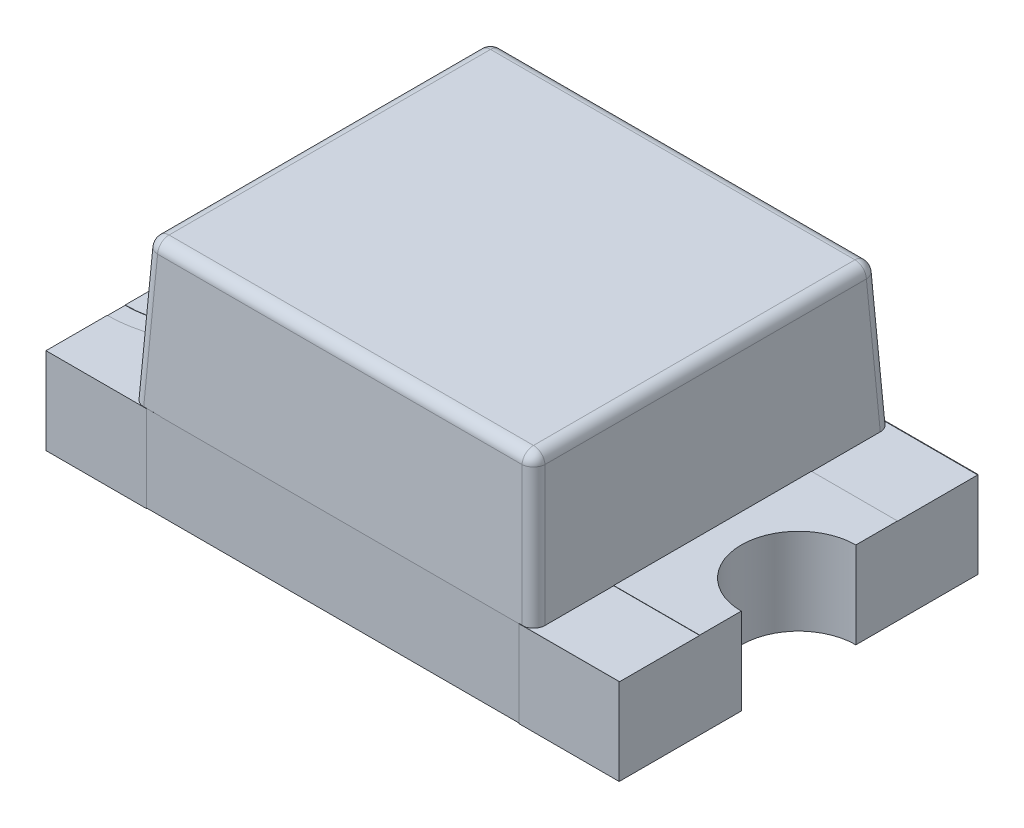
SolidWorks part; units mm, degrees
ref_plane "Front Plane" through (0, 0, 0) normal (0, 0, 1) x (1, 0, 0)
ref_plane "Top Plane" through (0, 0, 0) normal (0, 1, 0) x (1, 0, 0)
ref_plane "Right Plane" through (0, 0, 0) normal (1, 0, 0) x (0, 0, -1)
sketch "Sketch1" plane through (0, 0, 0) normal (0, 1, 0) x (1, 0, 0)
  line L0 (0, 1.2917) -> (0, -1.5721) construction
  line L1 (-2.2832, 0) -> (2.2044, 0) construction
  line L2 (-1, 0.2) -> (-1, 0.625)
  line L3 (1, -0.625) -> (-1, -0.625)
  line L4 (1, -0.625) -> (1, -0.2)
  line L5 (1, 0.625) -> (-1, 0.625)
  line L6 (-1, -0.625) -> (-1, -0.2)
  line L7 (1, -0.625) -> (-1, 0.625) construction
  line L8 (1, 0.625) -> (-1, -0.625) construction
  line L9 (1, 0.2) -> (1, 0.625)
  arc A0 (-1, 0.2) -> (-1, -0.2) centre (-1, 0) cw
  arc A1 (1, 0.2) -> (1, -0.2) centre (1, 0) ccw
  point P5 (0, 0)
  dimension "D1" = 0.2
  dimension "D2" = 1.25
  dimension "D3" = 2
extrude "Boss-Extrude1" add sketch "Sketch1" along normal mid plane 0.3
sketch "Sketch2" plane through (0, 0.15, 0) normal (0, 1, 0) x (1, 0, 0)
  line L0 (-1, 0.625) -> (-1, 0.2) construction
  line L1 (-1, -0.2) -> (-1, -0.625) construction
  line L2 (-1.3123, 0) -> (1.421, 0) construction
  line L3 (-1, 0.35) -> (-1, 0.2)
  line L4 (-1, -0.2) -> (-1, -0.35)
  line L5 (-1, 0.4125) -> (-1, 0.625)
  line L6 (-1, 0.625) -> (-0.6029, 0.625)
  line L7 (1, 0.625) -> (-1, 0.625) construction
  line L8 (-0.6029, 0.625) -> (-0.6029, 0.1118)
  line L9 (-1, -0.625) -> (1, -0.625) construction
  line L10 (-0.6029, -0.625) -> (-1, -0.625)
  line L11 (-1, -0.625) -> (-1, -0.4125)
  line L12 (-0.6029, -0.1118) -> (-0.6029, -0.625)
  line L13 (1, 0.2) -> (1, 0.625) construction
  line L14 (0.6, -0.345) -> (1, -0.345)
  line L15 (0.6, -0.345) -> (0.6, 0.345)
  line L16 (0.6, 0.345) -> (1, 0.345)
  line L17 (1, -0.345) -> (1, -0.2)
  line L18 (0.6, -0.345) -> (1, 0.345) construction
  line L19 (0.6, 0.345) -> (1, -0.345) construction
  line L20 (1, 0.2) -> (1, 0.345)
  arc A0 (-1, 0.35) -> (-1, -0.35) centre (-1, 0) cw
  arc A1 (-1, 0.2) -> (-1, -0.2) centre (-1, 0) cw
  arc A2 (-1, 0.4125) -> (-0.6029, 0.1118) centre (-1, 0) cw
  arc A3 (-0.6029, -0.1118) -> (-1, -0.4125) centre (-1, 0) cw
  arc A4 (1, -0.2) -> (1, 0.2) centre (1, 0) cw
  point P18 (-0.6029, 0.1118)
  point P29 (-0.6029, -0.1118)
  point P32 (0.8, 0)
  dimension "D1" = 0.35
  dimension "D2" = 0.28
  dimension "D3" = 0.28
  dimension "D4" = 0.4
extrude "Boss-Extrude2" add sketch "Sketch2" along normal blind 0.001
sketch "Sketch3" plane through (0, 0.15, 0) normal (0, 1, 0) x (1, 0, 0)
  line L0 (0, 0.625) -> (0, -0.625) construction
  line L1 (1, 0.625) -> (-0.6029, 0.625) construction
  line L2 (-0.6029, -0.625) -> (1, -0.625) construction
  line L3 (-0.9949, 0) -> (1.0141, 0) construction
  line L5 (0.7, -0.625) -> (-0.7, -0.625)
  line L6 (0.7, -0.625) -> (0.7, 0.625)
  line L7 (0.7, 0.625) -> (-0.7, 0.625)
  line L8 (-0.7, -0.625) -> (-0.7, 0.625)
  line L9 (0.7, -0.625) -> (-0.7, 0.625) construction
  line L10 (0.7, 0.625) -> (-0.7, -0.625) construction
  point P9 (0, 0)
  dimension "D1" = 1.4
extrude "Boss-Extrude3" add sketch "Sketch3" along normal blind 0.5 draft 3
fillet "Fillet1" radius 0.04 8 edges at (0.6869, 0.4, 0.6119) (0.6869, 0.4, -0.6119) (0.6738, 0.65, 0) (0, 0.65, -0.5988) (-0.6869, 0.4005, -0.6119) (-0.6738, 0.65, 0) (-0.6869, 0.4005, 0.6119) (0, 0.65, 0.5988)
sketch "Sketch4" plane through (0, 0, -0.625) normal (0, 0, -1) x (-1, 0, 0)
  line L0 (-1, -0.15) -> (1, -0.15) construction
  line L1 (1, 0.151) -> (0.65, 0.151)
  line L2 (1, 0.151) -> (1, -0.15)
  line L3 (1, -0.15) -> (0.65, -0.15)
  line L4 (0.65, 0.151) -> (0.65, -0.15)
  dimension "D1" = 0.35
extrude "Boss-Extrude4" add sketch "Sketch4" along normal blind 0.001
mirror "Mirror1" about plane through (0, 0, 0) normal (1, 0, 0) of "Boss-Extrude4"
mirror "Mirror2" about plane through (0, 0, 0) normal (0, 0, 1) of "Mirror1", "Boss-Extrude4"
sketch "Sketch5" plane through (0, -0.15, 0) normal (0, -1, 0) x (1, 0, 0)
  line L0 (0.65, -0.626) -> (1, -0.626) construction
  line L1 (1, 0.626) -> (0.65, 0.626)
  line L2 (1, 0.626) -> (1, 0.2)
  line L3 (1, -0.626) -> (0.65, -0.626)
  line L4 (0.65, 0.626) -> (0.65, -0.626)
  line L5 (1, -0.2) -> (1, -0.626)
  arc A0 (1, 0.2) -> (1, -0.2) centre (1, 0) ccw
extrude "Boss-Extrude5" add sketch "Sketch5" along normal blind 0.001
mirror "Mirror3" about plane through (0, 0, 0) normal (1, 0, 0) of "Boss-Extrude5"
sketch "Sketch6" plane through (0, -0.15, 0) normal (0, -1, 0) x (1, 0, 0)
  line L0 (-1.0481, 0) -> (0.9352, 0) construction
  line L1 (0, 0.625) -> (0, 0.0002) construction
  line L2 (-0.65, 0.625) -> (0.65, 0.625) construction
  line L3 (0.65, -0.625) -> (-0.65, -0.625) construction
  line L4 (-0.1398, 0.0002) -> (0.1238, 0.23)
  line L5 (0.1238, 0.23) -> (0.1238, -0.23)
  line L6 (-0.14, -0.23) -> (-0.14, -0.0002)
  line L7 (-0.14, 0.23) -> (-0.16, 0.23)
  line L8 (-0.16, 0.23) -> (-0.16, -0.23)
  line L9 (-0.1398, -0.0002) -> (0.1238, -0.23)
  line L10 (-0.16, -0.23) -> (-0.14, -0.23)
  line L11 (-0.14, 0.0002) -> (-0.1398, 0.0002)
  line L12 (-0.14, -0.0002) -> (-0.1398, -0.0002)
  line L13 (0, -0.0002) -> (0, -0.625) construction
  line L14 (-0.14, 0.0002) -> (-0.14, 0.23)
  point P16 (0.1238, 0)
  point P18 (-0.16, 0)
  dimension "D1" = 0.02
  dimension "D3" = 0.23
  dimension "D4" = 0.23
extrude "Cut-Extrude2" cut sketch "Sketch6" against normal blind 0.001
